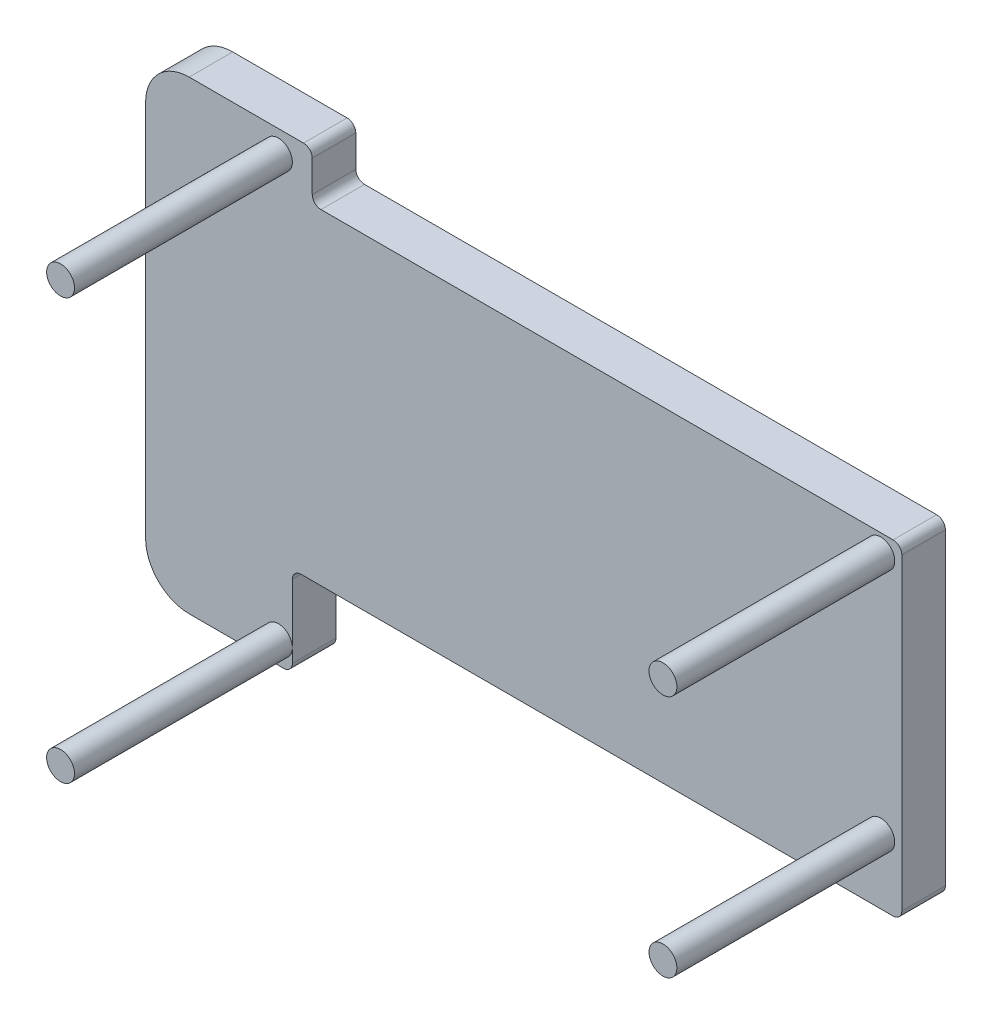
SolidWorks part; units mm, degrees
ref_plane "Front Plane" through (0, 0, 0) normal (0, 0, 1) x (1, 0, 0)
ref_plane "Top Plane" through (0, 0, 0) normal (0, 1, 0) x (1, 0, 0)
ref_plane "Right Plane" through (0, 0, 0) normal (1, 0, 0) x (0, 0, -1)
sketch "Sketch1" plane through (0, 0, 0) normal (0, 0, 1) x (1, 0, 0)
  line L0 (0, 0) -> (0, -29616.0158) construction
  line L1 (0, 0) -> (-29616.0158, 0) construction
  line L2 (-24.2667, 25.67) -> (-24.2667, 22.0667)
  line L3 (-27.5477, -26.67) -> (-38.3877, -26.67)
  line L4 (43.3877, -15.3186) -> (43.3877, 20.0667)
  line L5 (-25.2667, 26.67) -> (-38.3877, 26.67)
  line L6 (-43.3877, -21.67) -> (-43.3877, 21.67)
  line L8 (-26.5477, -24.13) -> (-26.5477, -17.3186)
  line L9 (-23.2667, 21.0667) -> (42.3877, 21.0667)
  line L10 (34.272, 21.0667) -> (-43.3877, -26.67) construction
  line L11 (-25.5477, -16.3186) -> (42.3877, -16.3186)
  line L12 (-26.5477, -24.13) -> (-26.5477, -25.67)
  line L13 (26.5477, -16.3186) -> (-43.3877, 26.67) construction
  circle A0 centre (-28.1477, -24.13) radius 1.6
  circle A1 centre (40.9778, -8.89) radius 1.6
  circle A2 centre (40.9778, 19.05) radius 1.6
  circle A3 centre (-28.1477, 24.13) radius 1.6
  arc A5 (-38.3877, 26.67) -> (-43.3877, 21.67) centre (-38.3877, 21.67) ccw
  arc A6 (-38.3877, -26.67) -> (-43.3877, -21.67) centre (-38.3877, -21.67) cw
  arc A8 (-24.2667, 25.67) -> (-25.2667, 26.67) centre (-25.2667, 25.67) ccw
  arc A9 (-24.2667, 22.0667) -> (-23.2667, 21.0667) centre (-23.2667, 22.0667) ccw
  arc A10 (43.3877, 20.0667) -> (42.3877, 21.0667) centre (42.3877, 20.0667) ccw
  arc A11 (-27.5477, -26.67) -> (-26.5477, -25.67) centre (-27.5477, -25.67) ccw
  arc A12 (42.3877, -16.3186) -> (43.3877, -15.3186) centre (42.3877, -15.3186) ccw
  arc A13 (-26.5477, -17.3186) -> (-25.5477, -16.3186) centre (-25.5477, -17.3186) cw
  point P5 (0, 0)
  point P19 (-26.5477, -16.3186)
  dimension "D1" = 3.2
  dimension "D2" = 3.2
  dimension "D3" = 3.2
  dimension "D9" = 1
  dimension "D11" = 1
  dimension "D12" = 1
  dimension "D13" = 1
  dimension "D7" = 1
  dimension "D4" = 15.24
  dimension "D5" = 2.54
  dimension "D6" = 17.78
  dimension "D10" = 50.8
extrude "Boss-Extrude2" add sketch "Sketch1" along normal blind 25 contours A0 | A3 | A1 | A2
extrude "Boss-Extrude4" add sketch "Sketch1<6>" against normal blind 5 contours L11 A12 L4 A10 L9 A9 L2 A8 L5 A5 L6 A6 L3 A11 L12 L8 A13
sketch "Sketch1<6>" plane through (0, 0, 0) normal (0, 0, 1) x (1, 0, 0) same geometry as "Sketch1"
